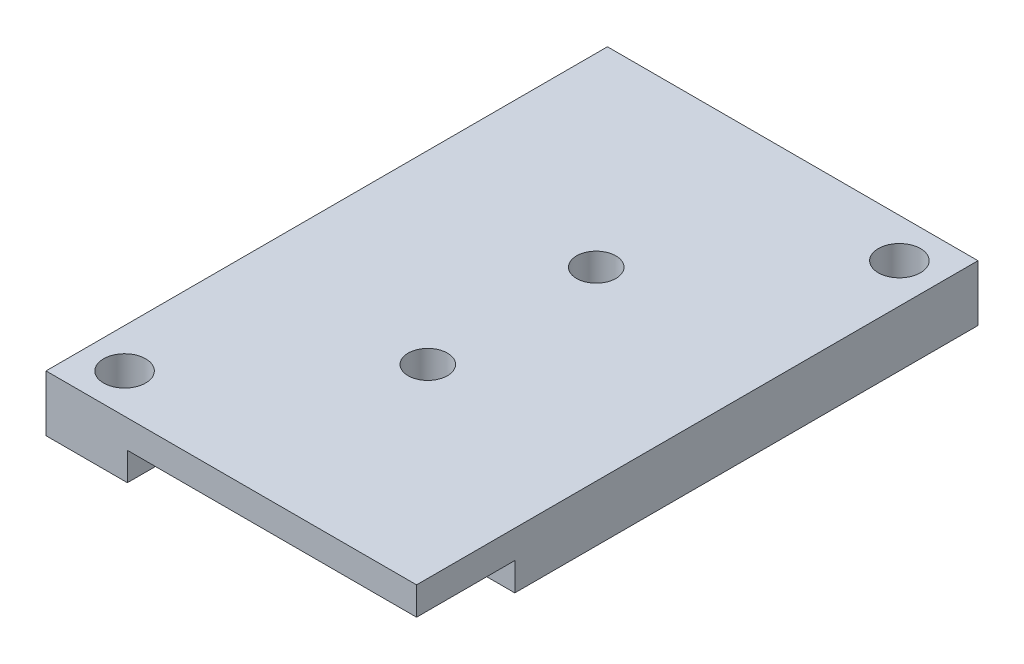
SolidWorks part; units mm, degrees
ref_plane "前视基准面" through (0, 0, 0) normal (0, 0, 1) x (1, 0, 0)
ref_plane "上视基准面" through (0, 0, 0) normal (0, 1, 0) x (1, 0, 0)
ref_plane "右视基准面" through (0, 0, 0) normal (1, 0, 0) x (0, 0, -1)
other "Configuration Table"
sketch "草图1" plane through (0, 0, 0) normal (0, 1, 0) x (1, 0, 0)
  line L1 (-6.6, 10) -> (6.6, 10)
  line L2 (-6.6, 10) -> (-6.6, -10)
  line L3 (-6.6, -10) -> (6.6, -10)
  line L4 (6.6, 10) -> (6.6, -10)
  line L5 (-6.6, 10) -> (6.6, -10) construction
  line L6 (-6.6, -10) -> (6.6, 10) construction
  circle A0 centre (-5.2, -8.6) radius 0.75
  circle A1 centre (5.2, 8.6) radius 0.75
  point P0 (0, 0)
  point P5 (3, -8.5)
  dimension "D7" = 1.5
  dimension "D1" = 20
  dimension "D2" = 13.2
  dimension "D3" = 1.4
  dimension "D4" = 1.4
  dimension "D5" = 1.4
  dimension "D6" = 1.4
extrude "凸台-拉伸1" add sketch "草图1" along normal blind 2 contours L2 L3 L4 L1
extrude "切除-拉伸2" cut sketch "草图1<3>" along normal through all contours A0 | A1
sketch "草图1<3>" plane through (0, 0, 0) normal (0, 1, 0) x (1, 0, 0) same geometry as "草图1"
sketch "草图2" plane through (0, 2, 0) normal (0, 1, 0) x (1, 0, 0)
  line L0 (6.6, 10) -> (6.6, -10) construction
  line L1 (-6.6, 10) -> (3.7, 10)
  line L2 (-6.6, 10) -> (-6.6, 6.5)
  line L3 (-6.6, 6.5) -> (3.7, 6.5)
  line L4 (3.7, 10) -> (3.7, 6.5)
  line L5 (6.6, -10) -> (-3.7, -10)
  line L6 (6.6, -10) -> (6.6, -6.5)
  line L7 (6.6, -6.5) -> (-3.7, -6.5)
  line L8 (-3.7, -10) -> (-3.7, -6.5)
  line L9 (-6.6, -10) -> (6.6, -10) construction
  line L12 (0, -6.5) -> (0, 6.5) construction
  line L13 (-2.5, 6.5) -> (2.5, 6.5)
  line L14 (-2.5, 6.5) -> (-2.5, -6.5)
  line L15 (-2.5, -6.5) -> (2.5, -6.5)
  line L16 (2.5, 6.5) -> (2.5, -6.5)
  circle A4 centre (0, 3) radius 0.7
  circle A5 centre (0, -3) radius 0.7
  dimension "D5" = 3
  dimension "D4" = 1.4
  dimension "D1" = 3.5
  dimension "D2" = 10.3
  dimension "D3" = 5
  dimension "D6" = 3
extrude "切除-拉伸1" cut sketch "草图2" along normal blind 1 from surface contours L12 L7 L16 L13 A4 A5 | L15 L12 A5 A4 L3 L14 | L12 A4 | A4 L12 | A5 L12 | L12 A5 | L1 L4 L3 L2 | L7 L8 L5 L6 region at (-1.2974, 2, 0) region at (1.2974, 2, 0) region at (0.2971, 2, -3) region at (-0.2971, 2, -3) region at (-0.2971, 2, 3) region at (0.2971, 2, 3) starting at face at (-5.2, 0, 9.35)
extrude "切除-拉伸3" cut sketch "草图2<4>" against normal through all contours A4 | A5
sketch "草图2<4>" plane through (0, 2, 0) normal (0, 1, 0) x (1, 0, 0) same geometry as "草图2"
